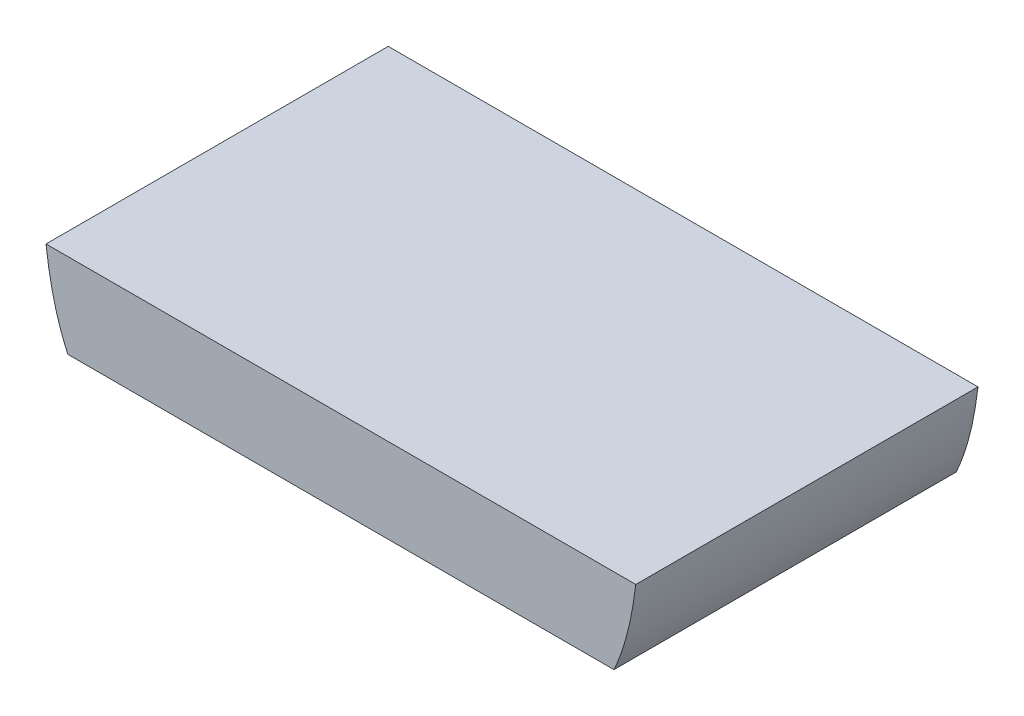
SolidWorks part; units mm, degrees
ref_plane "Front Plane" through (0, 0, 0) normal (0, 0, 1) x (1, 0, 0)
ref_plane "Top Plane" through (0, 0, 0) normal (0, 1, 0) x (1, 0, 0)
ref_plane "Right Plane" through (0, 0, 0) normal (1, 0, 0) x (0, 0, -1)
sketch "Sketch1" plane through (0, 0, 0) normal (0, 0, 1) x (1, 0, 0)
  line L0 (0, 0) -> (0, 222.758) construction
  line L2 (-350.1769, 222.758) -> (0, 222.758)
  line L3 (0, 222.758) -> (350.1769, 222.758)
  conic Q0 (350.1769, 222.758) -> (0, 0) control (323.6021, 0) rho 0.570465
  conic Q1 (-350.1769, 222.758) -> (0, 0) control (-323.6021, 0) rho 0.570465
extrude "Boss-Extrude1" add sketch "Sketch1" against normal blind 203.2 and the other way blind 203.2 contours Q0 Q1 L2 L3
sketch "Sketch6" plane through (0, 0, 0) normal (1, 0, 0) x (0, 0, -1)
  line L0 (0, 0) -> (402.7895, 12.7)
  line L1 (0, 0) -> (0, 317.8845) construction
  line L2 (0, 0) -> (-402.7895, 12.7)
  dimension "D1" = 12.7
ref_plane "Plane1" through (304.8, 0, 0) normal (1, 0, 0) x (0, 0, -1)
ref_plane "Plane2" [suppressed] through (0, 0, 401.32) normal (0, 0, 1) x (1, 0, 0)
sketch "Sketch29" plane through (0, 0, 0) normal (1, 0, 0) x (0, 0, -1)
  line L0 (0, 7.9367) -> (74.9675, 7.9367)
  line L1 (74.9675, 7.9367) -> (308.7791, 142.4931)
  line L3 (308.7791, 142.4931) -> (642.4614, 142.4931)
  point P6 (0, -63.5)
sweep "Engine Line" [suppressed] add path "Sketch29" circular profile diameter 12.7 parameters "D3"=12.7
sketch "Sketch42" plane through (0, 0, 0) normal (0, 0, 1) x (1, 0, 0)
  circle A0 centre (0, 6.35) radius 6.35
extrude "Boss-Extrude2" [suppressed] add sketch "Sketch42" against normal blind 635
sketch "Sketch43" plane through (0, 0, -203.2) normal (0, 0, -1) x (-1, 0, 0)
  circle A0 centre (0, 209.4482) radius 6.35
extrude "Boss-Extrude3" [suppressed] add sketch "Sketch43" along normal blind 142.748
ref_plane "Plane4" through (0, 0, 381) normal (0, 0, 1) x (1, 0, 0)
sketch "Sketch41" plane through (0, 0, 381) normal (0, 0, 1) x (1, 0, 0)
  line L0 (-0.3885, -71.0751) -> (-0.3885, 316.4102) construction
  conic Q0 (-0.3885, -71.0751) -> (301.9685, 246.7379) control (301.9685, -71.1416) rho 0.504796
  conic Q1 (-0.3885, -71.0751) -> (-302.7456, 246.7379) control (-302.7456, -71.1416) rho 0.504796
ref_plane "Plane5" through (350.1769, 0, 0) normal (1, 0, 0) x (0, 0, -1)
sketch "Sketch44" plane through (350.1769, 0, 0) normal (1, 0, 0) x (0, 0, -1)
  circle A0 centre (-360.0842, 200.1725) radius 12.7
extrude "Cut-Extrude1" cut sketch "Sketch44" against normal blind 25.4 rebuild error yes
sketch "Sketch45" plane through (0, 0, 0) normal (0, 0, 1) x (1, 0, 0)
  line L0 (-363.6888, 122.174) -> (403.1456, 122.174)
  line L1 (-350.1769, 222.758) -> (350.1769, 222.758) construction
  dimension "D1" = 100.584
split "Split1" trim tools "Sketch45" bodies to split 103 resulting bodies 127
